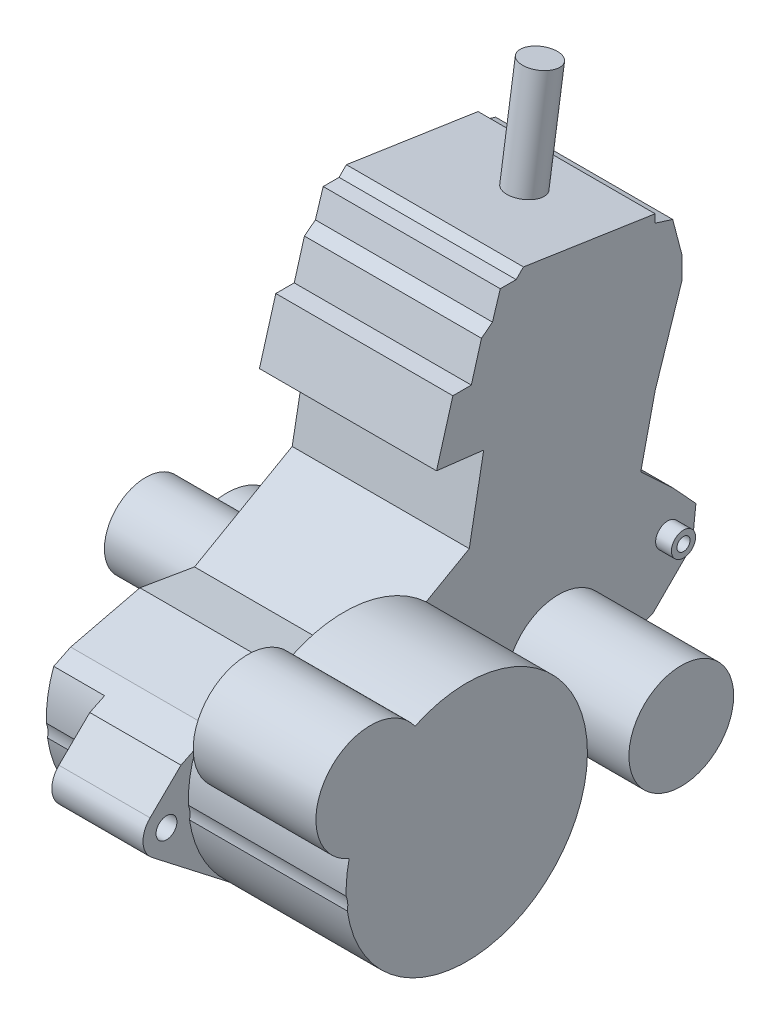
SolidWorks part; units mm, degrees
note: The reader was unsure of these and kept them because the rebuilt part matched: shared geometry of "Sketch3<3>", "Sketch3<4>", "Sketch3<5>", "Sketch3<6>".
ref_plane "Front Plane" through (0, 0, 0) normal (0, 0, 1) x (1, 0, 0)
ref_plane "Top Plane" through (0, 0, 0) normal (0, 1, 0) x (1, 0, 0)
ref_plane "Right Plane" through (0, 0, 0) normal (1, 0, 0) x (0, 0, -1)
sketch "Sketch3" plane through (0, 0, 0) normal (1, 0, 0) x (0, 0, -1)
  line L0 (9.6102, 25.7333) -> (43.6703, 25.7333) construction
  line L1 (4.4781, 12.1807) -> (26.8556, 34.0415)
  line L2 (98.6567, 208.7332) -> (647.3234, 208.7332) construction
  line L3 (26.8556, 34.0415) -> (49.8309, 45.213)
  line L4 (49.8309, 45.213) -> (99.9723, 57.2956)
  line L5 (99.9723, 57.2956) -> (139.5532, 50.6212)
  line L6 (139.5532, 50.6212) -> (210.2862, 90.8324)
  line L7 (5.9428, -13.4567) -> (66.0194, -60.0422)
  line L8 (210.2862, 90.8324) -> (220.7276, 147.4487)
  line L9 (220.7276, 147.4487) -> (186.5705, 151.5127)
  line L10 (186.5705, 151.5127) -> (198.4178, 192.7078)
  line L11 (198.4178, 192.7078) -> (211.7689, 192.7078)
  line L12 (211.7689, 192.7078) -> (219.1514, 218.3779)
  line L13 (219.1514, 218.3779) -> (227.0949, 224.5492)
  line L14 (227.0949, 224.5492) -> (232.7518, 242.6482)
  line L15 (232.7518, 242.6482) -> (244.2489, 242.6482)
  line L16 (244.2489, 242.6482) -> (249.5482, 247.9475)
  line L17 (249.5482, 247.9475) -> (344.9348, 233.5987)
  line L18 (344.9348, 233.5987) -> (344.9348, 227.6779)
  line L19 (344.9348, 227.6779) -> (357.6638, 223.6994)
  line L20 (357.6638, 223.6994) -> (364.2636, 198.4524)
  line L21 (364.2636, 198.4524) -> (364.2636, 181.6768)
  line L22 (364.2636, 181.6768) -> (344.9348, 122.6839)
  line L23 (344.9348, 122.6839) -> (334.5311, 76.9054)
  line L24 (334.5311, 76.9054) -> (357.6638, 55.3247)
  line L25 (357.6638, 55.3247) -> (374.4855, 37.117)
  line L26 (374.4855, 37.117) -> (371.7544, 12.1807)
  line L27 (371.7544, 12.1807) -> (343.2084, -16.3283)
  line L28 (343.2084, -16.3283) -> (306.2145, -29.7538)
  line L29 (111.451, -102.7483) -> (144.4771, -102.7483)
  line L30 (144.4771, -102.7483) -> (169.0027, -78.2227)
  line L31 (169.0027, -78.2227) -> (195.6075, -67.8813)
  line L32 (195.6075, -67.8813) -> (230.1514, -67.8813)
  line L33 (230.1514, -67.8813) -> (255.4133, -58.0619)
  line L34 (255.4133, -58.0619) -> (278.8828, -45.9763)
  line L35 (111.451, -102.7483) -> (88.7124, -72.7439)
  circle A0 centre (16.3776, 0) radius 15.2401
  circle A1 centre (119.5857, 9.0369) radius 87.4143
  circle A2 centre (16.3776, 0) radius 7.5463
  circle A3 centre (16.3776, 0) radius 17.0284
  circle A4 centre (274.9679, -8.2448) radius 37.934
  circle A5 centre (49.8309, 65.1427) radius 39.5214
  circle A6 centre (354.0423, 27.5753) radius 4.7471
  circle A7 centre (354.0423, 27.5753) radius 8.7657
  point P54 (0, 0)
  point P55 (300.6602, 33.0284)
  point P56 (0, 0)
  point P57 (300.1223, 32.2216)
  point P58 (332.7987, 29.5386)
  point P59 (332.7987, 40.8275)
  point P60 (330.4468, 23.7373)
  point P61 (295.4824, -16.558)
  point P62 (319.785, 31.4201)
  point P63 (0, 0)
  point P64 (326.7865, 49.017)
  point P65 (310.3228, 63.5044)
  point P66 (322.6038, 12.1807)
  point P67 (0, 0)
  point P68 (336.8561, 31.4201)
  point P69 (0, 0)
  point P70 (336.8561, 42.6654)
  point P71 (330.0398, 18.9631)
  point P72 (316.8718, 5.6402)
  point P73 (333.9127, 39.1023)
  point P74 (320.28, 31.8212)
  point P75 (0, 0)
  point P76 (288.1987, 75.4509)
  point P77 (298.7995, 153.4917)
  point P78 (295.4824, 69.0262)
  point P79 (325.1408, 50.6212)
  point P80 (349.876, 36.2601)
  point P81 (338.6327, 5.6402)
  point P82 (323.2134, -8.0704)
  point P83 (270.5307, -8.0704)
  point P84 (278.8828, -45.9763)
  point P85 (295.4824, -31.8419)
  point P86 (0, 0)
  point P87 (333.1717, 27.2655)
  point P88 (348.2698, 31.1203)
  point P89 (330.923, 0)
  point P90 (348.2698, 22.447)
  point P91 (343.4512, 38.5088)
  point P92 (343.4512, 20.2843)
  point P93 (358.555, 20.2843)
  point P94 (355.7214, 30.1073)
  point P95 (334.5641, -9.1102)
  point P96 (355.7214, 14.2393)
  point P97 (321.7186, 40.4971)
  point P98 (353.0768, 29.3517)
  point P99 (350.719, 40.1155)
  point P100 (375.0718, 20.2843)
  point P101 (375.0718, -3.1277)
  point P102 (348.4431, -18.8319)
  point P103 (375.0718, 35.5636)
  point P104 (362.554, 14.6248)
  point P105 (379.3962, 9.0369)
  point P106 (376.8926, 24.4114)
  point P107 (330.463, 39.6603)
  point P108 (343.2084, -16.3283)
  point P109 (0, 0)
  point P110 (344.9348, 122.6839)
  point P111 (334.5311, 76.9054)
  point P112 (278.8828, -22.2027)
  point P113 (306.2145, -29.7538)
  point P114 (362.554, 45.213)
  point P115 (349.7261, 24.4114)
  point P116 (0, 0)
  point P117 (362.554, 24.4114)
  point P118 (354.0423, 27.5753)
  point P119 (371.7544, 12.1807)
  point P120 (374.4855, 37.117)
  point P121 (357.6638, 55.3247)
extrude "Boss-Extrude1" add sketch "Sketch3" along normal mid plane 66.04 contours A1 A3 A0 | A5 L1 A3 A1 | L1 A5 A1 L3 | A3 L7 A1 | A2 | A1 A5 L4 L3 | A5 A1 A3 L8 L6 L5 L4 | A4 L28 L27 L26 L25 L24 L23 L22 L21 L20 L19 L18 L17 L16 L15 L14 L13 L12 L11 L10 L9 L8 A1 L35 L29 L30 L31 L32 L33 L34 A7 | A4 | A1 A3
extrude "Boss-Extrude2" add sketch "Sketch3<3>" along normal mid plane 139.7 separate body contours A7 A6 | A6
sketch "Sketch3<3>" plane through (0, 0, 0) normal (1, 0, 0) x (0, 0, -1) same geometry as "Sketch3"
extrude "Boss-Extrude3" add sketch "Sketch3<4>" along normal blind 25.4 from surface at 33.02 contours A5 A1 A3 L8 L6 L5 L4 | A1 A5 L4 L3 | A4 L28 L27 L26 L25 L24 L23 L22 L21 L20 L19 L18 L17 L16 L15 L14 L13 L12 L11 L10 L9 L8 A1 L35 L29 L30 L31 L32 L33 L34 A7 | A4
sketch "Sketch3<4>" plane through (0, 0, 0) normal (1, 0, 0) x (0, 0, -1) same geometry as "Sketch3"
extrude "Boss-Extrude4" add sketch "Sketch3<5>" along normal blind 88.9 from surface at 58.42 contours A1 A5 L1 L3 | L4 A5 A1 L3 | A1 A5 L4 L3 | A5 L4 L5 L6 L8 A1 | A5 A1 A3 L8 L6 L5 L4 | A4 | L1 A5 A1 L3
sketch "Sketch3<5>" plane through (0, 0, 0) normal (1, 0, 0) x (0, 0, -1) same geometry as "Sketch3"
extrude "Boss-Extrude5" add sketch "Sketch3<6>" against normal up to surface (36.83 mm away) from surface at -33.02 contours A5 A1 A3 L8 L6 L5 L4 | A1 A5 L4 L3 | A4 L28 L27 L26 L25 L24 L23 L22 L21 L20 L19 L18 L17 L16 L15 L14 L13 L12 L11 L10 L9 L8 A1 L35 L29 L30 L31 L32 L33 L34 A7 | A4
sketch "Sketch3<6>" plane through (0, 0, 0) normal (1, 0, 0) x (0, 0, -1) same geometry as "Sketch3"
sketch "Sketch4" plane through (-69.85, 0, 0) normal (-1, 0, 0) x (0, 0, 1)
  circle A0 centre (-167.668, 31.1227) radius 29.8835
  circle A1 centre (-226.3324, -21.3836) radius 43.2384
  point P2 (-226.3324, -21.3836)
extrude "Boss-Extrude6" add sketch "Sketch4" along normal blind 63.5
sketch "Sketch5" plane through (0, 279.1693, -41.9949) normal (0, 0.9889, -0.1488) x (1, 0, 0)
  line L1 (58.42, 320.4082) -> (-69.85, 320.4082) construction
  circle A0 centre (0, 269.6082) radius 12.7
  point P2 (0, 0)
  dimension "D1" = 25.4
  dimension "D2" = 50.8
extrude "Boss-Extrude7" add sketch "Sketch5" along normal blind 76.2
